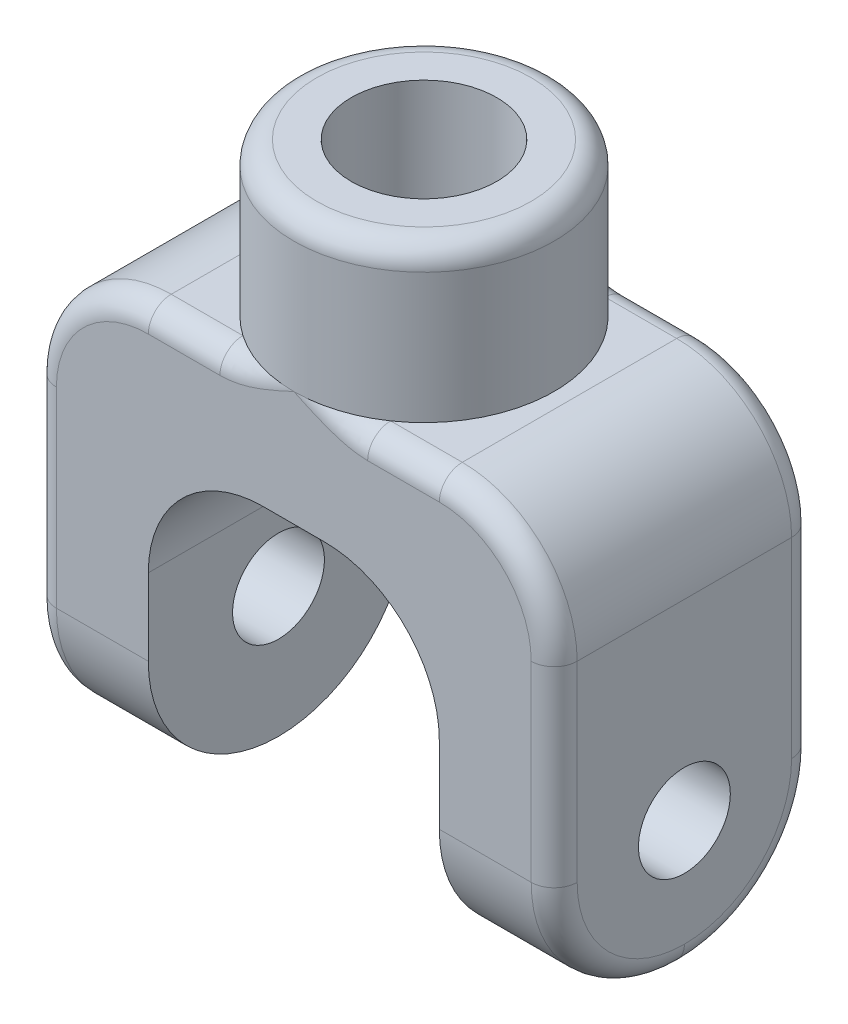
SolidWorks part; units mm, degrees
ref_plane "Front Plane" through (0, 0, 0) normal (0, 0, 1) x (1, 0, 0)
ref_plane "Top Plane" through (0, 0, 0) normal (0, 1, 0) x (1, 0, 0)
ref_plane "Right Plane" through (0, 0, 0) normal (1, 0, 0) x (0, 0, -1)
sketch "Sketch1" plane through (0, 0, 0) normal (0, 0, 1) x (1, 0, 0)
  line L0 (-34, 0) -> (-34, 57)
  line L1 (-34, 57) -> (34, 57)
  line L2 (34, 57) -> (34, 0)
  line L3 (0, 0) -> (0, 100.2723) construction
  line L4 (-19, 0) -> (-19, 42)
  line L5 (-19, 42) -> (19, 42)
  line L6 (19, 42) -> (19, 0)
  line L7 (19, 0) -> (34, 0)
  line L8 (-19, 0) -> (-34, 0)
  point P9 (0, 0)
  point P13 (0, 0)
  point P14 (-34, 0)
  point P15 (0, 0)
  dimension "D1" = 57
  dimension "D2" = 15
  dimension "D3" = 38
  dimension "D4" = 15
extrude "Boss-Extrude1" add sketch "Sketch1" along normal mid plane 34
fillet "Fillet1" radius 15 4 edges at (-19, 42, 0) (19, 42, 0) (-34, 57, 0) (34, 57, 0)
fillet "Fillet2" radius 17 4 edges at (-26.5, 0, -17) (26.5, 0, -17) (-26.5, 0, 17) (26.5, 0, 17)
hole_wizard "Hole1" positions "Sketch2" profile "Sketch3" legacy
sketch "Sketch2" plane through (34, 0, 0) normal (1, 0, 0) x (0, 0, -1)
  point P0 (0, 17)
sketch "Sketch3" plane through (34, 17, 0) normal (0, 1, 0) x (0, 0, -1)
  line L0 (0, 0) -> (0, 100)
  line L1 (0, 100) -> (6, 100)
  line L2 (6, 100) -> (6, 0)
  line L3 (6, 0) -> (0, 0)
  line L4 (0, 110) -> (0, -10) construction
  dimension "Diameter" = 12
  dimension "Depth" = 100
sketch "Sketch9" plane through (0, 57, 0) normal (0, 1, 0) x (1, 0, 0)
  circle A0 centre (0, 0) radius 17
  dimension "D1" = 34
extrude "Boss-Extrude3" add sketch "Sketch9" along normal blind 20
fillet "Fillet4" radius 3 17 edges at (34, 29.5, 17) (34, 4.9792, 12.0208) (34, 4.9792, -12.0208) (34, 29.5, -17) (29.6066, 52.6066, -17) (9.5, 57, -17) (-9.5, 57, -17) (-29.6066, 52.6066, -17) (-34, 29.5, -17) (-34, 4.9792, -12.0208) (-34, 4.9792, 12.0208) (-34, 29.5, 17) (-29.6066, 52.6066, 17) (-9.5, 57, 17) (9.5, 57, 17) (29.6066, 52.6066, 17) (0, 77, 17)
hole_wizard "Hole3" positions "Sketch10" profile "Sketch11" legacy
sketch "Sketch10" plane through (0, 77, 0) normal (0, 1, 0) x (1, 0, 0)
  point P0 (0, 0)
  point P4 (0, 0)
sketch "Sketch11" plane through (0, 77, 0) normal (1, 0, 0) x (0, 0, 1)
  line L0 (0, 0) -> (0, 100)
  line L1 (0, 100) -> (9.5, 100)
  line L2 (9.5, 100) -> (9.5, 0)
  line L3 (9.5, 0) -> (0, 0)
  line L4 (0, 110) -> (0, -10) construction
  dimension "Diameter" = 19
  dimension "Depth" = 100
